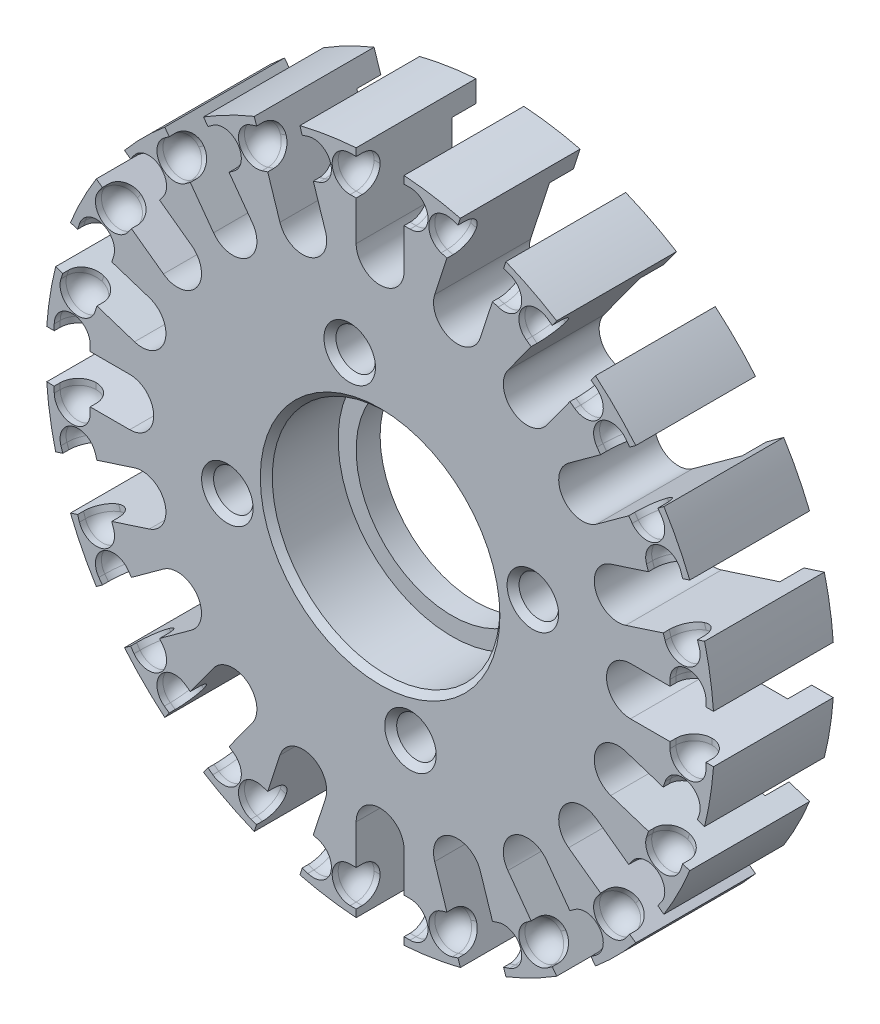
SolidWorks part; units mm, degrees
material "白色 POM"
ref_plane "前视基准面" through (0, 0, 0) normal (0, 0, 1) x (1, 0, 0)
ref_plane "上视基准面" through (0, 0, 0) normal (0, 1, 0) x (1, 0, 0)
ref_plane "右视基准面" through (0, 0, 0) normal (1, 0, 0) x (0, 0, -1)
sketch "草图1" plane through (0, 0, 0) normal (0, 0, 1) x (1, 0, 0)
  circle A0 centre (0, 0) radius 27.9
  dimension "D1" = 55.8
extrude "拉伸1" add sketch "草图1" along normal blind 10
sketch "草图10" plane through (0, 0, 10) normal (0, 0, 1) x (1, 0, 0)
  circle A0 centre (0, 0) radius 8
  dimension "D1" = 16
extrude "拉伸7" cut sketch "草图10" against normal up to surface (10 mm away) up to face at (27.9, 0, 0)
sketch "草图6" plane through (0, 0, 0) normal (0, 0, -1) x (-1, 0, 0)
  circle A0 centre (0, 0) radius 26.1
  dimension "D1" = 52.2
extrude "拉伸6" cut sketch "草图6" against normal blind 2
sketch "草图2" plane through (0, 0, 10) normal (0, 0, 1) x (1, 0, 0)
  circle A0 centre (0, 0) radius 9.5
  dimension "D1" = 19
extrude "拉伸2" cut sketch "草图2" against normal blind 6
sketch "草图3" plane through (0, 0, 10) normal (0, 0, 1) x (1, 0, 0)
  line L0 (0, 0) -> (0, 13) construction
  line L1 (0, 0) -> (-2.5362, 12.7502) construction
  circle A0 centre (0, 0) radius 13 construction
  circle A1 centre (-2.5362, 12.7502) radius 1.65
  dimension "D1" = 26
  dimension "D2" = 3.3
  dimension "D3" = 11.25
extrude "拉伸3" cut sketch "草图3" against normal blind 10
cosmetic thread "装饰螺纹线1" parameters "D2"=4
pattern_circular "阵列(圆周)1" count 4 over 360 about axis through (0, 0, 0) along (0, 0, 1) of "拉伸3"
cosmetic thread "装饰螺纹线2" parameters "D2"=4
cosmetic thread "装饰螺纹线3" parameters "D2"=4
cosmetic thread "装饰螺纹线4" parameters "D2"=4
sketch "草图4" plane through (0, 0, 10) normal (0, 0, 1) x (1, 0, 0)
  circle A0 centre (0, 0) radius 20 construction
  circle A1 centre (0, 20) radius 0.625
  dimension "D1" = 40
  dimension "D2" = 1.25
extrude "拉伸4" [suppressed] cut sketch "草图4" against normal blind 10
cosmetic thread "装饰螺纹线5" [suppressed] parameters "D2"=1.6
pattern_circular "阵列(圆周)2" [suppressed] count 6 every 60
sketch "草图5" plane through (0, 0, 10) normal (0, 0, 1) x (1, 0, 0)
  line L0 (-20.9, 2) -> (-27.8282, 2)
  line L1 (-20.9, -2) -> (-27.8282, -2)
  circle A0 centre (0, 0) radius 20.9 construction
  arc A1 (-20.9, -2) -> (-20.9, 2) centre (-20.9, 0) ccw
  arc A2 (-27.8282, 2) -> (-27.8282, -2) centre (0, 0) ccw
  circle A3 centre (0, 0) radius 27.9 construction
  dimension "D1" = 41.8
  dimension "D2" = 4
extrude "拉伸5" cut sketch "草图5" against normal blind 10
pattern_circular "阵列(圆周)3" count 20 over 360 about axis through (0, 0, 0) along (0, 0, 1) of "拉伸5"
sketch "草图8" plane through (0, 0, 10) normal (0, 0, 1) x (1, 0, 0)
  circle A0 centre (0, 0) radius 23
  dimension "D1" = 46
sketch "草图9" [suppressed] plane through (0, 0, 0) normal (1, 0, 0) x (0, 0, -1)
  line L0 (-8.5, -24) -> (-9.5, -24)
  line L1 (-9.5, -24) -> (-9.5, -22)
  line L2 (-8.5, -22) -> (-9.5, -22)
  line L3 (-9.5, 9.5) -> (-9.5, -9.5) construction
  line L4 (0, 0) -> (-9.5, 0) construction
  line L5 (-9.5, 9.1187) -> (-9.5, 5.271) construction
  arc A0 (-8.5, -24) -> (-8.5, -22) centre (-8.5, -23) ccw
  dimension "D1" = 1
  dimension "D4" = 23
  dimension "D2" = 1
  dimension "D3" = 1
sweep "切除-扫描1" [suppressed] cut profiles "草图9" path "草图8"
chamfer "倒角1" distance 0.5 angle 45 5 edges at (12.7502, 0.8862, 10) (0.8862, -12.7502, 10) (-12.7502, -0.8862, 10) (-0.8862, 12.7502, 10) (9.5, 0, 10)
chamfer "倒角2" [suppressed] distance 0.25 angle 45
sketch "草图11" plane through (0, 0, 10) normal (0, 0, 1) x (1, 0, 0)
  line L0 (-22.5, 3.75) -> (-22.5, -3.75) construction
  line L1 (-23.5, 3.75) -> (-21.5, 3.75) construction
  line L2 (-23.5, 3.75) -> (-23.5, -3.75)
  line L3 (-23.5, -3.75) -> (-21.5, -3.75)
  line L4 (-21.5, 3.75) -> (-21.5, -3.75)
  line L5 (-22.5, 0) -> (0, 0) construction
  line L6 (-20.8002, 11.5613) -> (-23.3654, 4.5136)
  line L7 (-23.3654, 4.5136) -> (-21.486, 3.8296) construction
  line L8 (-21.486, 3.8296) -> (-18.9208, 10.8773)
  line L9 (-18.9208, 10.8773) -> (-20.8002, 11.5613)
  line L10 (-19.8605, 11.2193) -> (-22.4257, 4.1716) construction
  line L11 (0, 0) -> (-21.1431, 7.6955) construction
  arc A0 (-21.486, 3.8296) -> (-21.5, 3.75) centre (0, 0) ccw
  arc A1 (-23.3654, 4.5136) -> (-23.5, 3.75) centre (0, 0) ccw
  arc A2 (-17.9751, 21.3379) -> (-21.3379, 17.9751) centre (0, 0) ccw construction
  arc A3 (-22.4257, 4.1716) -> (-22.5, 3.75) centre (0, 0) ccw construction
  dimension "D1" = 7.5
  dimension "D2" = 2
  dimension "D3" = 22.5
  dimension "D4" = 20
sketch "草图12" [suppressed] plane through (0, 0, 9.5) normal (0, 0, 1) x (1, 0, 0)
  line L1 (-20.3304, 11.3903) -> (-22.8955, 4.3426) construction
  line L3 (-22.3654, 5.7991) -> (-22.8955, 4.3426)
  line L5 (-23, 3.75) -> (-23, -3.75) construction
  line L7 (-23, 3.75) -> (-23, 0)
  line L9 (-24.1536, 6.45) -> (-18.6066, 4.4311) construction
  line L11 (-24.1536, 6.45) -> (-18.6066, 4.4311) construction
  line L13 (0, 0) -> (-24.5802, 0) construction
  arc A1 (-22.8955, 4.3426) -> (-23, 3.75) centre (0, 0) ccw construction
  arc A3 (-22.8955, 4.3426) -> (-23, 3.75) centre (0, 0) ccw
sketch "草图13" [suppressed] plane through (0, 0, 0) normal (0, 1, 0) x (1, 0, 0)
  line L0 (0, -9.5) -> (-24.5802, -9.5) construction
  line L1 (-24, -9.5) -> (-22, -9.5)
  line L2 (-24, -9.5) -> (-24, -7.5)
  line L3 (-24, -7.5) -> (-22, -7.5)
  line L4 (-22, -9.5) -> (-22, -7.5)
  line L5 (-23, -7.5) -> (-23, -9.5) construction
  dimension "D1" = 2
  dimension "D2" = 2
sweep "切除-扫描2" [suppressed] cut profiles "草图13" path "草图12"
sketch "草图15" plane through (0, 0, 10) normal (0, 0, 1) x (1, 0, 0)
  line L0 (-25.7, 4) -> (-25.7, -4) construction
  line L2 (-27.2, 2.5) -> (-27.2, -2.5)
  line L4 (-24.2, 2.5) -> (-24.2, -2.5)
  line L5 (-25.7, 0) -> (0, 0) construction
  arc A0 (-27.2, -2.5) -> (-24.2, -2.5) centre (-25.7, -2.5) ccw
  arc A1 (-24.2, 2.5) -> (-27.2, 2.5) centre (-25.7, 2.5) ccw
  dimension "D1" = 25.7
  dimension "D2" = 3
  dimension "D3" = 8
extrude "拉伸10" cut sketch "草图15" against normal blind 2
fillet "圆角2" [suppressed] radius 1
fillet "圆角3" radius 1.5 6 edges at (-24.2, -2.25, 8) (-24.2, 2.25, 8) (-27.2, -2.25, 8) (-27.2, 2.25, 8) (-25.7, -4, 8) (-25.7, 4, 8)
pattern_circular "阵列(圆周)6" count 20 over 360 about axis through (0, 0, 0) along (0, 0, 1) of "拉伸10", "圆角3"
sketch "草图17" plane through (0, 0, 2) normal (0, 0, -1) x (-1, 0, 0)
  line L0 (0, 0) -> (-11.667, 17.4609) construction
  line L1 (0, 0) -> (2.5362, 12.7502) construction
  circle A0 centre (0, 0) radius 21 construction
  dimension "D1" = 42
  dimension "D2" = 45
sketch "草图19" plane through (0, 0, 2) normal (0, 0, -1) x (-1, 0, 0)
  line L0 (0, 0) -> (-18.4555, 18.4555) construction
  circle A0 centre (0, 0) radius 23.9 construction
  circle A1 centre (-16.8999, 16.8999) radius 0.75
  arc A2 (-16.9141, 19.8777) -> (-19.8777, 16.9141) centre (0, 0) ccw construction
  dimension "D1" = 47.8
  dimension "D2" = 1.5
extrude "切除-拉伸1" cut sketch "草图19" against normal blind 6
cosmetic thread "装饰螺纹线6" parameters "D2"=2
pattern_circular "阵列(圆周)7" count 4 every 90 about axis through (0, 0, 0) along (0, 0, 1) of "切除-拉伸1"
